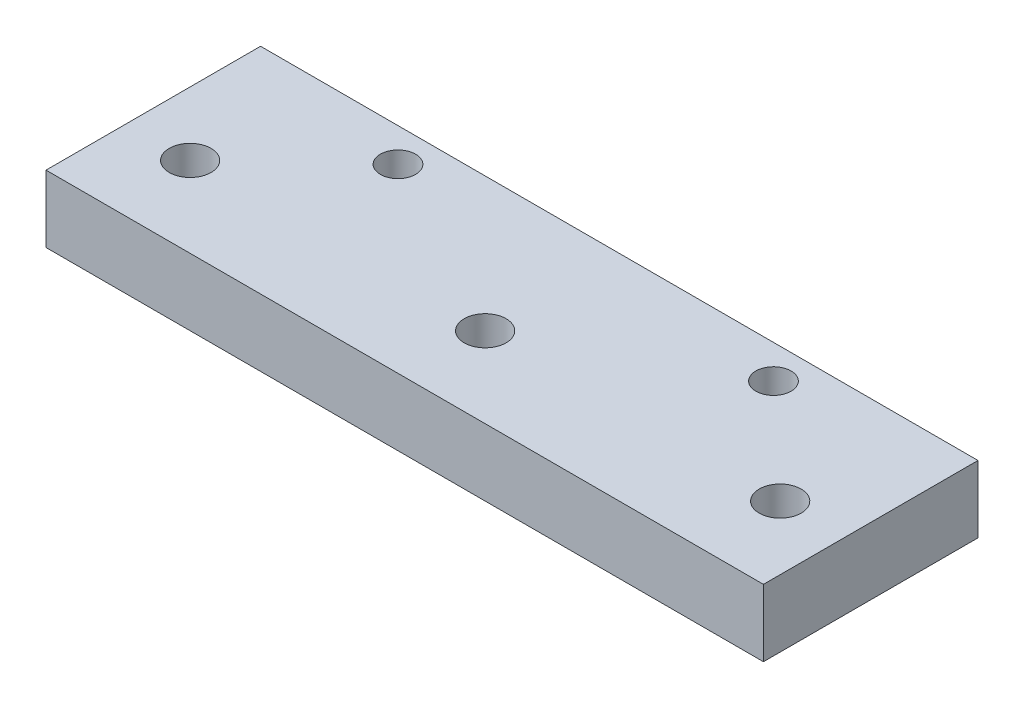
SolidWorks part; units mm, degrees
ref_plane "Front Plane" through (0, 0, 0) normal (0, 0, 1) x (1, 0, 0)
ref_plane "Top Plane" through (0, 0, 0) normal (0, 1, 0) x (1, 0, 0)
ref_plane "Right Plane" through (0, 0, 0) normal (1, 0, 0) x (0, 0, -1)
sketch "Sketch1" plane through (0, 0, 0) normal (0, 1, 0) x (1, 0, 0)
  line L1 (-169.8625, -50.8) -> (169.8625, -50.8)
  line L2 (-169.8625, -50.8) -> (-169.8625, 50.8)
  line L3 (-169.8625, 50.8) -> (169.8625, 50.8)
  line L4 (169.8625, -50.8) -> (169.8625, 50.8)
  line L5 (-169.8625, -50.8) -> (169.8625, 50.8) construction
  line L6 (-169.8625, 50.8) -> (169.8625, -50.8) construction
  point P0 (0, 0)
  dimension "D1" = 169.8625
  dimension "D2" = 50.8
extrude "Boss-Extrude1" add sketch "Sketch1" along normal mid plane 31.75
sketch "Sketch2" plane through (0, 0, 0) normal (0, 1, 0) x (1, 0, 0)
  circle A0 centre (-139.7127, -12.7) radius 9.9187
  circle A1 centre (-0.0127, -12.7) radius 9.9187
  circle A2 centre (139.6873, -12.7) radius 9.9187
  point P6 (0, 0)
  dimension "D1" = 19.8374
  dimension "D2" = 19.8374
  dimension "D3" = 19.8374
  dimension "D4" = 139.7
  dimension "D5" = 279.4
  dimension "D6" = 139.6873
  dimension "D7" = 12.7
extrude "Cut-Extrude2" cut sketch "Sketch2" along normal blind 63.5 from offset 15.875 offset against normal yes
sketch "Sketch3" plane through (0, 0, 0) normal (0, 1, 0) x (1, 0, 0)
  circle A0 centre (-139.7127, -12.7) radius 15.0876
  circle A1 centre (-0.0127, -12.7) radius 15.0876
  circle A2 centre (139.6873, -12.7) radius 15.0876
  point P6 (0, 0)
  dimension "D1" = 30.1752
  dimension "D2" = 30.1752
  dimension "D3" = 30.1752
  dimension "D4" = 139.7
  dimension "D5" = 279.4
  dimension "D6" = 139.6873
  dimension "D7" = 12.7
extrude "Cut-Extrude4" cut sketch "Sketch3" along normal blind 3.175 from offset 15.875 offset against normal yes
sketch "Sketch4" plane through (0, 0, 0) normal (0, 1, 0) x (1, 0, 0)
  circle A0 centre (-88.9127, 34.925) radius 8.3312
  circle A1 centre (88.8873, 34.925) radius 8.3312
  point P4 (0, 0)
  dimension "D1" = 16.6624
  dimension "D2" = 16.6624
  dimension "D3" = 177.8
  dimension "D4" = 88.9127
  dimension "D5" = 34.925
extrude "Cut-Extrude6" cut sketch "Sketch4" along normal blind 63.5 from offset 15.875 offset against normal yes
